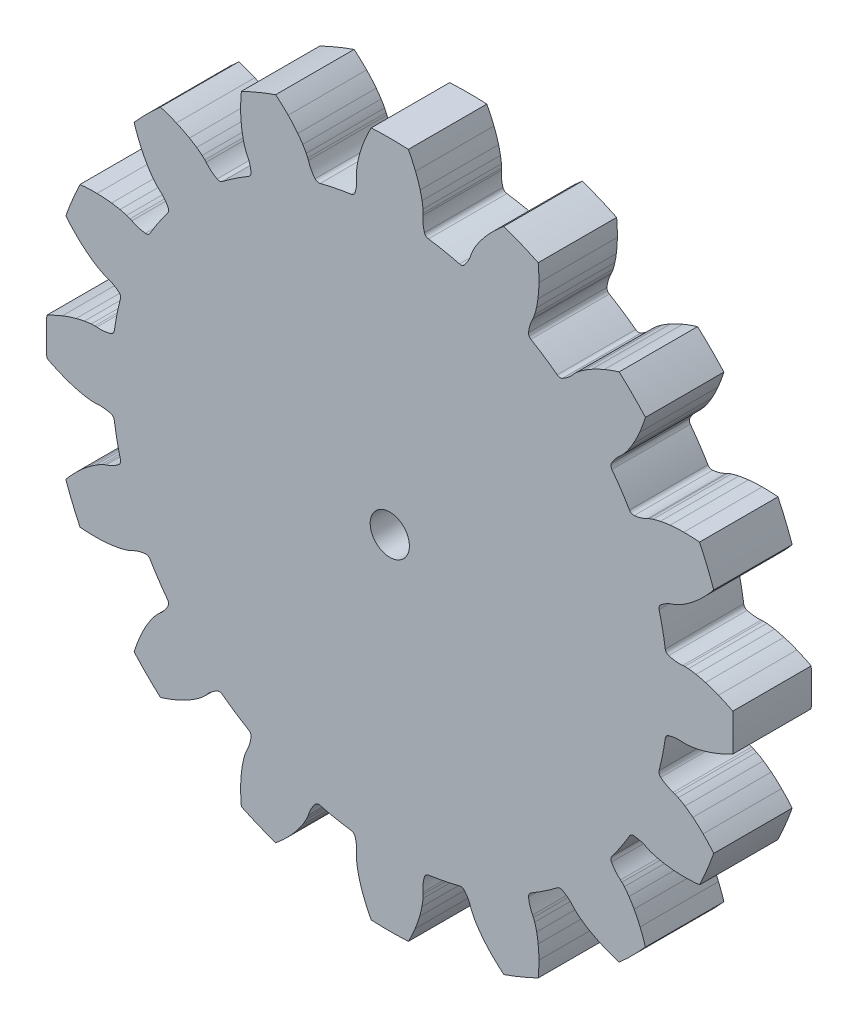
SolidWorks part; units mm, degrees
ref_plane "Front Plane" through (0, 0, 0) normal (0, 0, 1) x (1, 0, 0)
ref_plane "Top Plane" through (0, 0, 0) normal (0, 1, 0) x (1, 0, 0)
ref_plane "Right Plane" through (0, 0, 0) normal (1, 0, 0) x (0, 0, -1)
sketch "Model" plane through (0, 0, 0) normal (0, 0, 1) x (1, 0, 0)
  arc A1 (22.0867, -4.3933) -> (22.3008, -3.1302) centre (0, 0) ccw
  arc A2 (22.5768, -2.8062) -> (22.3008, -3.1302) centre (22.6938, -3.1854) ccw
  arc A3 (23.7172, -2.6934) -> (22.5768, -2.8062) centre (23.4244, -5.5546) ccw
  arc A4 (23.7172, -2.6934) -> (23.875, -2.7001) centre (23.8525, -1.3714) ccw
  arc A5 (23.875, -2.7001) -> (24.166, -2.6858) centre (23.7984, 1.8268) ccw
  arc A6 (24.166, -2.6858) -> (24.7196, -2.6123) centre (23.7188, 2.8051) ccw
  arc A7 (24.7196, -2.6123) -> (25.3944, -2.4589) centre (23.1829, 5.7052) ccw
  arc A8 (25.3944, -2.4589) -> (26.5158, -2.0827) centre (22.7771, 7.2035) ccw
  arc A9 (26.5158, -2.0827) -> (27.7636, -1.505) centre (21.4631, 10.4673) ccw
  arc A10 (27.7636, -1.505) -> (27.7636, 1.505) centre (0, 0) ccw
  arc A11 (27.7636, 1.505) -> (26.6084, 2.0452) centre (21.4412, -10.5088) ccw
  arc A12 (26.6084, 2.0452) -> (25.5573, 2.4131) centre (22.6674, -7.5296) ccw
  arc A13 (25.5573, 2.4131) -> (24.7891, 2.5997) centre (23.086, -6.0895) ccw
  arc A14 (24.7891, 2.5997) -> (24.166, 2.6858) centre (23.7109, -2.901) ccw
  arc A15 (24.166, 2.6858) -> (23.875, 2.7001) centre (23.7984, -1.8268) ccw
  arc A16 (23.875, 2.7001) -> (23.7172, 2.6934) centre (23.8525, 1.3713) ccw
  arc A17 (22.5768, 2.8062) -> (23.7172, 2.6934) centre (23.4244, 5.5546) ccw
  arc A18 (22.3008, 3.1302) -> (22.5768, 2.8062) centre (22.6938, 3.1854) ccw
  arc A19 (22.3008, 3.1302) -> (21.8011, 5.6422) centre (0, 0) ccw
  arc A20 (21.9322, 6.0472) -> (21.8011, 5.6422) centre (22.1853, 5.7416) ccw
  arc A21 (22.9426, 6.5878) -> (21.9322, 6.0472) centre (23.767, 3.8323) ccw
  arc A22 (22.9426, 6.5878) -> (23.0909, 6.642) centre (22.5616, 7.861) ccw
  arc A23 (23.0909, 6.642) -> (23.3543, 6.7666) centre (21.2878, 10.795) ccw
  arc A24 (23.3543, 6.7666) -> (23.8377, 7.0463) centre (20.8398, 11.6683) ccw
  arc A25 (23.8377, 7.0463) -> (24.4023, 7.4463) centre (19.235, 14.1426) ccw
  arc A26 (24.4023, 7.4463) -> (25.2944, 8.223) centre (18.2866, 15.3716) ccw
  arc A27 (25.2944, 8.223) -> (26.2261, 9.2342) centre (15.8237, 17.884) ccw
  arc A28 (26.2261, 9.2342) -> (25.0742, 12.0151) centre (0, 0) ccw
  arc A29 (25.0742, 12.0151) -> (23.8003, 12.0722) centre (23.8306, -1.5037) ccw
  arc A30 (23.8003, 12.0722) -> (22.6884, 12.0098) centre (23.8234, 1.718) ccw
  arc A31 (22.6884, 12.0098) -> (21.9073, 11.8881) centre (23.659, 3.2086) ccw
  arc A32 (21.9073, 11.8881) -> (21.2987, 11.7293) centre (23.0162, 6.3936) ccw
  arc A33 (21.2987, 11.7293) -> (21.0243, 11.6311) centre (22.686, 7.4196) ccw
  arc A34 (21.0243, 11.6311) -> (20.8811, 11.5646) centre (21.512, 10.3949) ccw
  arc A35 (19.7844, 11.2324) -> (20.8811, 11.5646) centre (19.5157, 14.096) ccw
  arc A36 (19.4054, 11.4261) -> (19.7844, 11.2324) centre (19.7473, 11.6274) ccw
  arc A37 (19.4054, 11.4261) -> (17.9825, 13.5557) centre (0, 0) ccw
  arc A38 (17.9485, 13.98) -> (17.9825, 13.5557) centre (18.2993, 13.7945) ccw
  arc A39 (18.6751, 14.8661) -> (17.9485, 13.98) centre (20.4913, 12.6358) ccw
  arc A40 (18.6751, 14.8661) -> (18.7914, 14.9729) centre (17.836, 15.8966) ccw
  arc A41 (18.7914, 14.9729) -> (18.9871, 15.1888) centre (15.5363, 18.1198) ccw
  arc A42 (18.9871, 15.1888) -> (19.3266, 15.6322) centre (14.7882, 18.7552) ccw
  arc A43 (19.3266, 15.6322) -> (19.6952, 16.2179) centre (12.3586, 20.427) ccw
  arc A44 (19.6952, 16.2179) -> (20.2222, 17.2768) centre (11.0122, 21.1995) ccw
  arc A45 (20.2222, 17.2768) -> (20.696, 18.5676) centre (7.7752, 22.5782) ccw
  arc A46 (20.696, 18.5676) -> (18.5676, 20.696) centre (0, 0) ccw
  arc A47 (18.5676, 20.696) -> (17.3688, 20.2612) centre (22.5921, 7.7303) ccw
  arc A48 (17.3688, 20.2612) -> (16.3654, 19.7781) centre (21.3525, 10.7041) ccw
  arc A49 (16.3654, 19.7781) -> (15.6903, 19.3668) centre (20.6302, 12.0183) ccw
  arc A50 (15.6903, 19.3668) -> (15.1888, 18.9871) centre (18.8175, 14.7148) ccw
  arc A51 (15.1888, 18.9871) -> (14.9729, 18.7914) centre (18.1198, 15.5363) ccw
  arc A52 (14.9729, 18.7914) -> (14.8661, 18.6751) centre (15.8966, 17.836) ccw
  arc A53 (13.98, 17.9485) -> (14.8661, 18.6751) centre (12.6358, 20.4913) ccw
  arc A54 (13.5557, 17.9825) -> (13.98, 17.9485) centre (13.7945, 18.2993) ccw
  arc A55 (13.5557, 17.9825) -> (11.4261, 19.4054) centre (0, 0) ccw
  arc A56 (11.2324, 19.7844) -> (11.4261, 19.4054) centre (11.6274, 19.7473) ccw
  arc A57 (11.5646, 20.8811) -> (11.2324, 19.7844) centre (14.096, 19.5157) ccw
  arc A58 (11.5646, 20.8811) -> (11.6311, 21.0243) centre (10.3949, 21.512) ccw
  arc A59 (11.6311, 21.0243) -> (11.7293, 21.2987) centre (7.4196, 22.686) ccw
  arc A60 (11.7293, 21.2987) -> (11.8733, 21.8383) centre (6.4852, 22.9867) ccw
  arc A61 (11.8733, 21.8383) -> (11.9897, 22.5204) centre (3.6008, 23.6015) ccw
  arc A62 (11.9897, 22.5204) -> (12.0713, 23.7004) centre (2.0612, 23.7999) ccw
  arc A63 (12.0713, 23.7004) -> (12.0151, 25.0742) centre (-1.4569, 23.8349) ccw
  arc A64 (12.0151, 25.0742) -> (9.2342, 26.2261) centre (0, 0) ccw
  arc A65 (9.2342, 26.2261) -> (8.293, 25.3657) centre (17.9141, 15.7875) ccw
  arc A66 (8.293, 25.3657) -> (7.5509, 24.5353) centre (15.6309, 18.0605) ccw
  arc A67 (7.5509, 24.5353) -> (7.0846, 23.897) centre (14.4606, 18.9983) ccw
  arc A68 (7.0846, 23.897) -> (6.7666, 23.3543) centre (11.754, 20.7959) ccw
  arc A69 (6.7666, 23.3543) -> (6.642, 23.0909) centre (10.795, 21.2878) ccw
  arc A70 (6.642, 23.0909) -> (6.5878, 22.9426) centre (7.861, 22.5616) ccw
  arc A71 (6.0472, 21.9322) -> (6.5878, 22.9426) centre (3.8323, 23.767) ccw
  arc A72 (5.6422, 21.8011) -> (6.0472, 21.9322) centre (5.7416, 22.1853) ccw
  arc A73 (5.6422, 21.8011) -> (3.1302, 22.3008) centre (0, 0) ccw
  arc A74 (2.8062, 22.5768) -> (3.1302, 22.3008) centre (3.1854, 22.6938) ccw
  arc A75 (2.6934, 23.7172) -> (2.8062, 22.5768) centre (5.5546, 23.4244) ccw
  arc A76 (2.6934, 23.7172) -> (2.7001, 23.875) centre (1.3714, 23.8525) ccw
  arc A77 (2.7001, 23.875) -> (2.6858, 24.166) centre (-1.8268, 23.7984) ccw
  arc A78 (2.6858, 24.166) -> (2.6123, 24.7196) centre (-2.8051, 23.7188) ccw
  arc A79 (2.6123, 24.7196) -> (2.4589, 25.3944) centre (-5.7052, 23.1829) ccw
  arc A80 (2.4589, 25.3944) -> (2.0827, 26.5158) centre (-7.2035, 22.7771) ccw
  arc A81 (2.0827, 26.5158) -> (1.505, 27.7636) centre (-10.4673, 21.4631) ccw
  arc A82 (1.505, 27.7636) -> (-1.505, 27.7636) centre (0, 0) ccw
  arc A83 (-1.505, 27.7636) -> (-2.0452, 26.6084) centre (10.5088, 21.4412) ccw
  arc A84 (-2.0452, 26.6084) -> (-2.4131, 25.5573) centre (7.5296, 22.6674) ccw
  arc A85 (-2.4131, 25.5573) -> (-2.5997, 24.7891) centre (6.0895, 23.086) ccw
  arc A86 (-2.5997, 24.7891) -> (-2.6858, 24.166) centre (2.901, 23.7109) ccw
  arc A87 (-2.6858, 24.166) -> (-2.7001, 23.875) centre (1.8268, 23.7984) ccw
  arc A88 (-2.7001, 23.875) -> (-2.6934, 23.7172) centre (-1.3713, 23.8525) ccw
  arc A89 (-2.8062, 22.5768) -> (-2.6934, 23.7172) centre (-5.5546, 23.4244) ccw
  arc A90 (-3.1302, 22.3008) -> (-2.8062, 22.5768) centre (-3.1854, 22.6938) ccw
  arc A91 (-3.1302, 22.3008) -> (-5.6422, 21.8011) centre (0, 0) ccw
  arc A92 (-6.0472, 21.9322) -> (-5.6422, 21.8011) centre (-5.7416, 22.1853) ccw
  arc A93 (-6.5878, 22.9426) -> (-6.0472, 21.9322) centre (-3.8323, 23.767) ccw
  arc A94 (-6.5878, 22.9426) -> (-6.642, 23.0909) centre (-7.861, 22.5616) ccw
  arc A95 (-6.642, 23.0909) -> (-6.7666, 23.3543) centre (-10.795, 21.2878) ccw
  arc A96 (-6.7666, 23.3543) -> (-7.0463, 23.8377) centre (-11.6683, 20.8398) ccw
  arc A97 (-7.0463, 23.8377) -> (-7.4463, 24.4023) centre (-14.1426, 19.235) ccw
  arc A98 (-7.4463, 24.4023) -> (-8.223, 25.2944) centre (-15.3716, 18.2866) ccw
  arc A99 (-8.223, 25.2944) -> (-9.2342, 26.2261) centre (-17.884, 15.8237) ccw
  arc A100 (-9.2342, 26.2261) -> (-12.0151, 25.0742) centre (0, 0) ccw
  arc A101 (-12.0151, 25.0742) -> (-12.0722, 23.8003) centre (1.5037, 23.8306) ccw
  arc A102 (-12.0722, 23.8003) -> (-12.0098, 22.6884) centre (-1.718, 23.8234) ccw
  arc A103 (-12.0098, 22.6884) -> (-11.8881, 21.9073) centre (-3.2086, 23.659) ccw
  arc A104 (-11.8881, 21.9073) -> (-11.7293, 21.2987) centre (-6.3936, 23.0162) ccw
  arc A105 (-11.7293, 21.2987) -> (-11.6311, 21.0243) centre (-7.4196, 22.686) ccw
  arc A106 (-11.6311, 21.0243) -> (-11.5646, 20.8811) centre (-10.3949, 21.512) ccw
  arc A107 (-11.2324, 19.7844) -> (-11.5646, 20.8811) centre (-14.096, 19.5157) ccw
  arc A108 (-11.4261, 19.4054) -> (-11.2324, 19.7844) centre (-11.6274, 19.7473) ccw
  arc A109 (-11.4261, 19.4054) -> (-13.5557, 17.9825) centre (0, 0) ccw
  arc A110 (-13.98, 17.9485) -> (-13.5557, 17.9825) centre (-13.7945, 18.2993) ccw
  arc A111 (-14.8661, 18.6751) -> (-13.98, 17.9485) centre (-12.6358, 20.4913) ccw
  arc A112 (-14.8661, 18.6751) -> (-14.9729, 18.7914) centre (-15.8966, 17.836) ccw
  arc A113 (-14.9729, 18.7914) -> (-15.1888, 18.9871) centre (-18.1198, 15.5363) ccw
  arc A114 (-15.1888, 18.9871) -> (-15.6322, 19.3266) centre (-18.7552, 14.7882) ccw
  arc A115 (-15.6322, 19.3266) -> (-16.2179, 19.6952) centre (-20.427, 12.3586) ccw
  arc A116 (-16.2179, 19.6952) -> (-17.2768, 20.2222) centre (-21.1995, 11.0122) ccw
  arc A117 (-17.2768, 20.2222) -> (-18.5676, 20.696) centre (-22.5782, 7.7752) ccw
  arc A118 (-18.5676, 20.696) -> (-20.696, 18.5676) centre (0, 0) ccw
  arc A119 (-20.696, 18.5676) -> (-20.2612, 17.3688) centre (-7.7303, 22.5921) ccw
  arc A120 (-20.2612, 17.3688) -> (-19.7781, 16.3654) centre (-10.7041, 21.3525) ccw
  arc A121 (-19.7781, 16.3654) -> (-19.3668, 15.6903) centre (-12.0183, 20.6302) ccw
  arc A122 (-19.3668, 15.6903) -> (-18.9871, 15.1888) centre (-14.7148, 18.8175) ccw
  arc A123 (-18.9871, 15.1888) -> (-18.7914, 14.9729) centre (-15.5363, 18.1198) ccw
  arc A124 (-18.7914, 14.9729) -> (-18.6751, 14.8661) centre (-17.836, 15.8966) ccw
  arc A125 (-17.9485, 13.98) -> (-18.6751, 14.8661) centre (-20.4913, 12.6358) ccw
  arc A126 (-17.9825, 13.5557) -> (-17.9485, 13.98) centre (-18.2993, 13.7945) ccw
  arc A127 (-17.9825, 13.5557) -> (-19.4054, 11.4261) centre (0, 0) ccw
  arc A128 (-19.7844, 11.2324) -> (-19.4054, 11.4261) centre (-19.7473, 11.6274) ccw
  arc A129 (-20.8811, 11.5646) -> (-19.7844, 11.2324) centre (-19.5157, 14.096) ccw
  arc A130 (-20.8811, 11.5646) -> (-21.0243, 11.6311) centre (-21.512, 10.3949) ccw
  arc A131 (-21.0243, 11.6311) -> (-21.2987, 11.7293) centre (-22.686, 7.4196) ccw
  arc A132 (-21.2987, 11.7293) -> (-21.8383, 11.8733) centre (-22.9867, 6.4852) ccw
  arc A133 (-21.8383, 11.8733) -> (-22.5204, 11.9897) centre (-23.6015, 3.6008) ccw
  arc A134 (-22.5204, 11.9897) -> (-23.7004, 12.0713) centre (-23.7999, 2.0612) ccw
  arc A135 (-23.7004, 12.0713) -> (-25.0742, 12.0151) centre (-23.8349, -1.4569) ccw
  arc A136 (-25.0742, 12.0151) -> (-26.2261, 9.2342) centre (0, 0) ccw
  arc A137 (-26.2261, 9.2342) -> (-25.3657, 8.293) centre (-15.7875, 17.9141) ccw
  arc A138 (-25.3657, 8.293) -> (-24.5353, 7.5509) centre (-18.0605, 15.6309) ccw
  arc A139 (-24.5353, 7.5509) -> (-23.897, 7.0846) centre (-18.9983, 14.4606) ccw
  arc A140 (-23.897, 7.0846) -> (-23.3543, 6.7666) centre (-20.7959, 11.754) ccw
  arc A141 (-23.3543, 6.7666) -> (-23.0909, 6.642) centre (-21.2878, 10.795) ccw
  arc A142 (-23.0909, 6.642) -> (-22.9426, 6.5878) centre (-22.5616, 7.861) ccw
  arc A143 (-21.9322, 6.0472) -> (-22.9426, 6.5878) centre (-23.767, 3.8323) ccw
  arc A144 (-21.8011, 5.6422) -> (-21.9322, 6.0472) centre (-22.1853, 5.7416) ccw
  arc A145 (-21.8011, 5.6422) -> (-22.3008, 3.1302) centre (0, 0) ccw
  arc A146 (-22.5768, 2.8062) -> (-22.3008, 3.1302) centre (-22.6938, 3.1854) ccw
  arc A147 (-23.7172, 2.6934) -> (-22.5768, 2.8062) centre (-23.4244, 5.5546) ccw
  arc A148 (-23.7172, 2.6934) -> (-23.875, 2.7001) centre (-23.8525, 1.3714) ccw
  arc A149 (-23.875, 2.7001) -> (-24.166, 2.6858) centre (-23.7984, -1.8268) ccw
  arc A150 (-24.166, 2.6858) -> (-24.7196, 2.6123) centre (-23.7188, -2.8051) ccw
  arc A151 (-24.7196, 2.6123) -> (-25.3944, 2.4589) centre (-23.1829, -5.7052) ccw
  arc A152 (-25.3944, 2.4589) -> (-26.5158, 2.0827) centre (-22.7771, -7.2035) ccw
  arc A153 (-26.5158, 2.0827) -> (-27.7636, 1.505) centre (-21.4631, -10.4673) ccw
  arc A154 (-27.7636, 1.505) -> (-27.7636, -1.505) centre (0, 0) ccw
  arc A155 (-27.7636, -1.505) -> (-26.6084, -2.0452) centre (-21.4412, 10.5088) ccw
  arc A156 (-26.6084, -2.0452) -> (-25.5573, -2.4131) centre (-22.6674, 7.5296) ccw
  arc A157 (-25.5573, -2.4131) -> (-24.7891, -2.5997) centre (-23.086, 6.0895) ccw
  arc A158 (-24.7891, -2.5997) -> (-24.166, -2.6858) centre (-23.7109, 2.901) ccw
  arc A159 (-24.166, -2.6858) -> (-23.875, -2.7001) centre (-23.7984, 1.8268) ccw
  arc A160 (-23.875, -2.7001) -> (-23.7172, -2.6934) centre (-23.8525, -1.3713) ccw
  arc A161 (-22.5768, -2.8062) -> (-23.7172, -2.6934) centre (-23.4244, -5.5546) ccw
  arc A162 (-22.3008, -3.1302) -> (-22.5768, -2.8062) centre (-22.6938, -3.1854) ccw
  arc A163 (-22.3008, -3.1302) -> (-21.8011, -5.6422) centre (0, 0) ccw
  arc A164 (-21.9322, -6.0472) -> (-21.8011, -5.6422) centre (-22.1853, -5.7416) ccw
  arc A165 (-22.9426, -6.5878) -> (-21.9322, -6.0472) centre (-23.767, -3.8323) ccw
  arc A166 (-22.9426, -6.5878) -> (-23.0909, -6.642) centre (-22.5616, -7.861) ccw
  arc A167 (-23.0909, -6.642) -> (-23.3543, -6.7666) centre (-21.2878, -10.795) ccw
  arc A168 (-23.3543, -6.7666) -> (-23.8377, -7.0463) centre (-20.8398, -11.6683) ccw
  arc A169 (-23.8377, -7.0463) -> (-24.4023, -7.4463) centre (-19.235, -14.1426) ccw
  arc A170 (-24.4023, -7.4463) -> (-25.2944, -8.223) centre (-18.2866, -15.3716) ccw
  arc A171 (-25.2944, -8.223) -> (-26.2261, -9.2342) centre (-15.8237, -17.884) ccw
  arc A172 (-26.2261, -9.2342) -> (-25.0742, -12.0151) centre (0, 0) ccw
  arc A173 (-25.0742, -12.0151) -> (-23.8003, -12.0722) centre (-23.8306, 1.5037) ccw
  arc A174 (-23.8003, -12.0722) -> (-22.6884, -12.0098) centre (-23.8234, -1.718) ccw
  arc A175 (-22.6884, -12.0098) -> (-21.9073, -11.8881) centre (-23.659, -3.2086) ccw
  arc A176 (-21.9073, -11.8881) -> (-21.2987, -11.7293) centre (-23.0162, -6.3936) ccw
  arc A177 (-21.2987, -11.7293) -> (-21.0243, -11.6311) centre (-22.686, -7.4196) ccw
  arc A178 (-21.0243, -11.6311) -> (-20.8811, -11.5646) centre (-21.512, -10.3949) ccw
  arc A179 (-19.7844, -11.2324) -> (-20.8811, -11.5646) centre (-19.5157, -14.096) ccw
  arc A180 (-19.4054, -11.4261) -> (-19.7844, -11.2324) centre (-19.7473, -11.6274) ccw
  arc A181 (-19.4054, -11.4261) -> (-17.9825, -13.5557) centre (0, 0) ccw
  arc A182 (-17.9485, -13.98) -> (-17.9825, -13.5557) centre (-18.2993, -13.7945) ccw
  arc A183 (-18.6751, -14.8661) -> (-17.9485, -13.98) centre (-20.4913, -12.6358) ccw
  arc A184 (-18.6751, -14.8661) -> (-18.7914, -14.9729) centre (-17.836, -15.8966) ccw
  arc A185 (-18.7914, -14.9729) -> (-18.9871, -15.1888) centre (-15.5363, -18.1198) ccw
  arc A186 (-18.9871, -15.1888) -> (-19.3266, -15.6322) centre (-14.7882, -18.7552) ccw
  arc A187 (-19.3266, -15.6322) -> (-19.6952, -16.2179) centre (-12.3586, -20.427) ccw
  arc A188 (-19.6952, -16.2179) -> (-20.2222, -17.2768) centre (-11.0122, -21.1995) ccw
  arc A189 (-20.2222, -17.2768) -> (-20.696, -18.5676) centre (-7.7752, -22.5782) ccw
  arc A190 (-20.696, -18.5676) -> (-18.5676, -20.696) centre (0, 0) ccw
  arc A191 (-18.5676, -20.696) -> (-17.3688, -20.2612) centre (-22.5921, -7.7303) ccw
  arc A192 (-17.3688, -20.2612) -> (-16.3654, -19.7781) centre (-21.3525, -10.7041) ccw
  arc A193 (-16.3654, -19.7781) -> (-15.6903, -19.3668) centre (-20.6302, -12.0183) ccw
  arc A194 (-15.6903, -19.3668) -> (-15.1888, -18.9871) centre (-18.8175, -14.7148) ccw
  arc A195 (-15.1888, -18.9871) -> (-14.9729, -18.7914) centre (-18.1198, -15.5363) ccw
  arc A196 (-14.9729, -18.7914) -> (-14.8661, -18.6751) centre (-15.8966, -17.836) ccw
  arc A197 (-13.98, -17.9485) -> (-14.8661, -18.6751) centre (-12.6358, -20.4913) ccw
  arc A198 (-13.5557, -17.9825) -> (-13.98, -17.9485) centre (-13.7945, -18.2993) ccw
  arc A199 (-13.5557, -17.9825) -> (-11.4261, -19.4054) centre (0, 0) ccw
  arc A200 (-11.2324, -19.7844) -> (-11.4261, -19.4054) centre (-11.6274, -19.7473) ccw
  arc A201 (-11.5646, -20.8811) -> (-11.2324, -19.7844) centre (-14.096, -19.5157) ccw
  arc A202 (-11.5646, -20.8811) -> (-11.6311, -21.0243) centre (-10.3949, -21.512) ccw
  arc A203 (-11.6311, -21.0243) -> (-11.7293, -21.2987) centre (-7.4196, -22.686) ccw
  arc A204 (-11.7293, -21.2987) -> (-11.8733, -21.8383) centre (-6.4852, -22.9867) ccw
  arc A205 (-11.8733, -21.8383) -> (-11.9897, -22.5204) centre (-3.6008, -23.6015) ccw
  arc A206 (-11.9897, -22.5204) -> (-12.0713, -23.7004) centre (-2.0612, -23.7999) ccw
  arc A207 (-12.0713, -23.7004) -> (-12.0151, -25.0742) centre (1.4569, -23.8349) ccw
  arc A208 (-12.0151, -25.0742) -> (-9.2342, -26.2261) centre (0, 0) ccw
  arc A209 (-9.2342, -26.2261) -> (-8.293, -25.3657) centre (-17.9141, -15.7875) ccw
  arc A210 (-8.293, -25.3657) -> (-7.5509, -24.5353) centre (-15.6309, -18.0605) ccw
  arc A211 (-7.5509, -24.5353) -> (-7.0846, -23.897) centre (-14.4606, -18.9983) ccw
  arc A212 (-7.0846, -23.897) -> (-6.7666, -23.3543) centre (-11.754, -20.7959) ccw
  arc A213 (-6.7666, -23.3543) -> (-6.642, -23.0909) centre (-10.795, -21.2878) ccw
  arc A214 (-6.642, -23.0909) -> (-6.5878, -22.9426) centre (-7.861, -22.5616) ccw
  arc A215 (-6.0472, -21.9322) -> (-6.5878, -22.9426) centre (-3.8323, -23.767) ccw
  arc A216 (-5.6422, -21.8011) -> (-6.0472, -21.9322) centre (-5.7416, -22.1853) ccw
  arc A217 (-5.6422, -21.8011) -> (-3.1302, -22.3008) centre (0, 0) ccw
  arc A218 (-2.8062, -22.5768) -> (-3.1302, -22.3008) centre (-3.1854, -22.6938) ccw
  arc A219 (-2.6934, -23.7172) -> (-2.8062, -22.5768) centre (-5.5546, -23.4244) ccw
  arc A220 (-2.6934, -23.7172) -> (-2.7001, -23.875) centre (-1.3714, -23.8525) ccw
  arc A221 (-2.7001, -23.875) -> (-2.6858, -24.166) centre (1.8268, -23.7984) ccw
  arc A222 (-2.6858, -24.166) -> (-2.6123, -24.7196) centre (2.8051, -23.7188) ccw
  arc A223 (-2.6123, -24.7196) -> (-2.4589, -25.3944) centre (5.7052, -23.1829) ccw
  arc A224 (-2.4589, -25.3944) -> (-2.0827, -26.5158) centre (7.2035, -22.7771) ccw
  arc A225 (-2.0827, -26.5158) -> (-1.505, -27.7636) centre (10.4673, -21.4631) ccw
  arc A226 (-1.505, -27.7636) -> (1.505, -27.7636) centre (0, 0) ccw
  arc A227 (1.505, -27.7636) -> (2.0452, -26.6084) centre (-10.5088, -21.4412) ccw
  arc A228 (2.0452, -26.6084) -> (2.4131, -25.5573) centre (-7.5296, -22.6674) ccw
  arc A229 (2.4131, -25.5573) -> (2.5997, -24.7891) centre (-6.0895, -23.086) ccw
  arc A230 (2.5997, -24.7891) -> (2.6858, -24.166) centre (-2.901, -23.7109) ccw
  arc A231 (2.6858, -24.166) -> (2.7001, -23.875) centre (-1.8268, -23.7984) ccw
  arc A232 (2.7001, -23.875) -> (2.6934, -23.7172) centre (1.3713, -23.8525) ccw
  arc A233 (2.8062, -22.5768) -> (2.6934, -23.7172) centre (5.5546, -23.4244) ccw
  arc A234 (3.1302, -22.3008) -> (2.8062, -22.5768) centre (3.1854, -22.6938) ccw
  arc A235 (3.1302, -22.3008) -> (5.6422, -21.8011) centre (0, 0) ccw
  arc A236 (6.0472, -21.9322) -> (5.6422, -21.8011) centre (5.7416, -22.1853) ccw
  arc A237 (6.5878, -22.9426) -> (6.0472, -21.9322) centre (3.8323, -23.767) ccw
  arc A238 (6.5878, -22.9426) -> (6.642, -23.0909) centre (7.861, -22.5616) ccw
  arc A239 (6.642, -23.0909) -> (6.7666, -23.3543) centre (10.795, -21.2878) ccw
  arc A240 (6.7666, -23.3543) -> (7.0463, -23.8377) centre (11.6683, -20.8398) ccw
  arc A241 (7.0463, -23.8377) -> (7.4463, -24.4023) centre (14.1426, -19.235) ccw
  arc A242 (7.4463, -24.4023) -> (8.223, -25.2944) centre (15.3716, -18.2866) ccw
  arc A243 (8.223, -25.2944) -> (9.2342, -26.2261) centre (17.884, -15.8237) ccw
  arc A244 (9.2342, -26.2261) -> (12.0151, -25.0742) centre (0, 0) ccw
  arc A245 (12.0151, -25.0742) -> (12.0722, -23.8003) centre (-1.5037, -23.8306) ccw
  arc A246 (12.0722, -23.8003) -> (12.0098, -22.6884) centre (1.718, -23.8234) ccw
  arc A247 (12.0098, -22.6884) -> (11.8881, -21.9073) centre (3.2086, -23.659) ccw
  arc A248 (11.8881, -21.9073) -> (11.7293, -21.2987) centre (6.3936, -23.0162) ccw
  arc A249 (11.7293, -21.2987) -> (11.6311, -21.0243) centre (7.4196, -22.686) ccw
  arc A250 (11.6311, -21.0243) -> (11.5646, -20.8811) centre (10.3949, -21.512) ccw
  arc A251 (11.2324, -19.7844) -> (11.5646, -20.8811) centre (14.096, -19.5157) ccw
  arc A252 (11.4261, -19.4054) -> (11.2324, -19.7844) centre (11.6274, -19.7473) ccw
  arc A253 (11.4261, -19.4054) -> (13.5557, -17.9825) centre (0, 0) ccw
  arc A254 (13.98, -17.9485) -> (13.5557, -17.9825) centre (13.7945, -18.2993) ccw
  arc A255 (14.8661, -18.6751) -> (13.98, -17.9485) centre (12.6358, -20.4913) ccw
  arc A256 (14.8661, -18.6751) -> (14.9729, -18.7914) centre (15.8966, -17.836) ccw
  arc A257 (14.9729, -18.7914) -> (15.1888, -18.9871) centre (18.1198, -15.5363) ccw
  arc A258 (15.1888, -18.9871) -> (15.6322, -19.3266) centre (18.7552, -14.7882) ccw
  arc A259 (15.6322, -19.3266) -> (16.2179, -19.6952) centre (20.427, -12.3586) ccw
  arc A260 (16.2179, -19.6952) -> (17.2768, -20.2222) centre (21.1995, -11.0122) ccw
  arc A261 (17.2768, -20.2222) -> (18.5676, -20.696) centre (22.5782, -7.7752) ccw
  arc A262 (18.5676, -20.696) -> (20.696, -18.5676) centre (0, 0) ccw
  arc A263 (20.696, -18.5676) -> (20.2612, -17.3688) centre (7.7303, -22.5921) ccw
  arc A264 (20.2612, -17.3688) -> (19.7781, -16.3654) centre (10.7041, -21.3525) ccw
  arc A265 (19.7781, -16.3654) -> (19.3668, -15.6903) centre (12.0183, -20.6302) ccw
  arc A266 (19.3668, -15.6903) -> (18.9871, -15.1888) centre (14.7148, -18.8175) ccw
  arc A267 (18.9871, -15.1888) -> (18.7914, -14.9729) centre (15.5363, -18.1198) ccw
  arc A268 (18.7914, -14.9729) -> (18.6751, -14.8661) centre (17.836, -15.8966) ccw
  arc A269 (17.9485, -13.98) -> (18.6751, -14.8661) centre (20.4913, -12.6358) ccw
  arc A270 (17.9825, -13.5557) -> (17.9485, -13.98) centre (18.2993, -13.7945) ccw
  arc A271 (17.9825, -13.5557) -> (19.4054, -11.4261) centre (0, 0) ccw
  arc A272 (19.7844, -11.2324) -> (19.4054, -11.4261) centre (19.7473, -11.6274) ccw
  arc A273 (20.8811, -11.5646) -> (19.7844, -11.2324) centre (19.5157, -14.096) ccw
  arc A274 (20.8811, -11.5646) -> (21.0243, -11.6311) centre (21.512, -10.3949) ccw
  arc A275 (21.0243, -11.6311) -> (21.2987, -11.7293) centre (22.686, -7.4196) ccw
  arc A276 (21.2987, -11.7293) -> (21.8383, -11.8733) centre (22.9867, -6.4852) ccw
  arc A277 (21.8383, -11.8733) -> (22.5204, -11.9897) centre (23.6015, -3.6008) ccw
  arc A278 (22.5204, -11.9897) -> (23.7004, -12.0713) centre (23.7999, -2.0612) ccw
  arc A279 (23.7004, -12.0713) -> (25.0742, -12.0151) centre (23.8349, 1.4569) ccw
  arc A280 (25.0742, -12.0151) -> (26.2261, -9.2342) centre (0, 0) ccw
  arc A281 (26.2261, -9.2342) -> (25.3657, -8.293) centre (15.7875, -17.9141) ccw
  arc A282 (25.3657, -8.293) -> (24.5353, -7.5509) centre (18.0605, -15.6309) ccw
  arc A283 (24.5353, -7.5509) -> (23.897, -7.0846) centre (18.9983, -14.4606) ccw
  arc A284 (23.897, -7.0846) -> (23.3543, -6.7666) centre (20.7959, -11.754) ccw
  arc A285 (23.3543, -6.7666) -> (23.0909, -6.642) centre (21.2878, -10.795) ccw
  arc A286 (23.0909, -6.642) -> (22.9426, -6.5878) centre (22.5616, -7.861) ccw
  arc A287 (21.9322, -6.0472) -> (22.9426, -6.5878) centre (23.767, -3.8323) ccw
  arc A288 (21.8011, -5.6422) -> (21.9322, -6.0472) centre (22.1853, -5.7416) ccw
  arc A289 (21.8011, -5.6422) -> (22.0867, -4.3933) centre (0, 0) ccw
extrude "Boss-Extrude1" add sketch "Model" along normal blind 6.35
sketch "Sketch2" plane through (0, 0, 6.35) normal (0, 0, 1) x (1, 0, 0)
  circle A0 centre (0, 0) radius 1.5875
  dimension "D1" = 3.175
extrude "Cut-Extrude1" cut sketch "Sketch2" against normal through all
